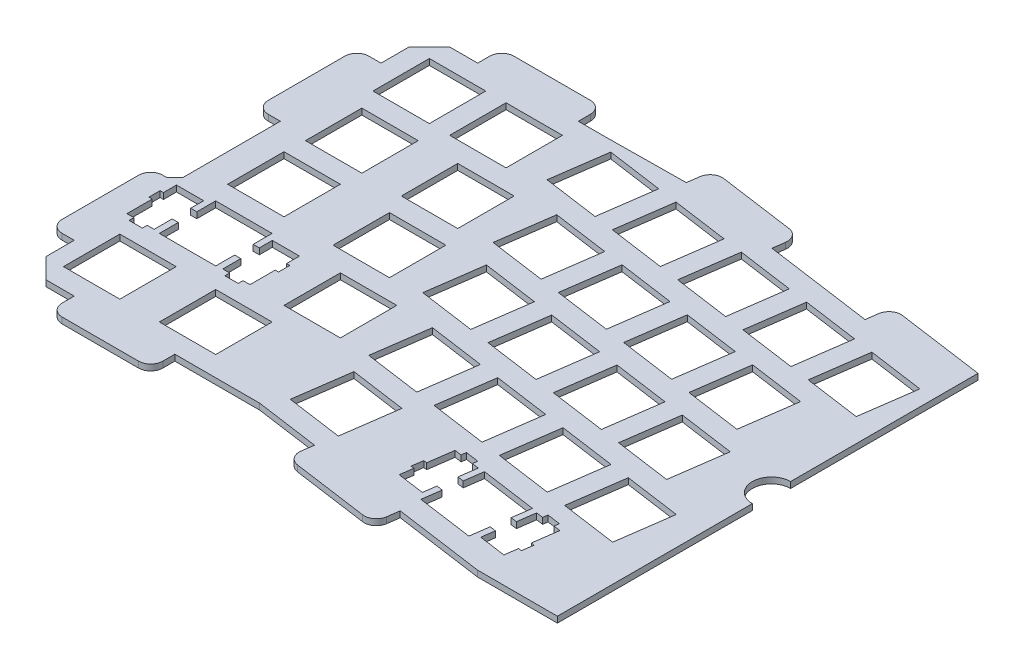
SolidWorks part; units mm, degrees
material "ABS PC"
ref_plane "Front Plane" through (0, 0, 0) normal (0, 0, 1) x (1, 0, 0)
ref_plane "Top Plane" through (0, 0, 0) normal (0, 1, 0) x (1, 0, 0)
ref_plane "Right Plane" through (0, 0, 0) normal (1, 0, 0) x (0, 0, -1)
sketch "Sketch1" plane through (0, 0, 0) normal (0, 1, 0) x (1, 0, 0)
  line L57 (39.046, 95.2051) -> (-4.333, 95.2051)
  line L58 (-4.333, 95.2051) -> (-4.333, -5)
  line L59 (-4.333, -5) -> (53.7464, -5)
  line L60 (53.7464, -5) -> (116.699, -13.8474)
  line L61 (116.699, -13.8474) -> (136.5182, -13.8474)
  line L62 (136.5182, -13.8474) -> (136.5182, 84.5577)
  line L63 (136.5182, 84.5577) -> (39.4665, 98.1974)
  line L64 (39.4665, 98.1974) -> (39.046, 95.2051)
  line L65 (39.046, 95.2051) -> (-4.333, 95.2051)
  line L66 (-4.333, 95.2051) -> (-4.333, -5)
  line L67 (-4.333, -5) -> (53.7464, -5)
  line L68 (53.7464, -5) -> (116.699, -13.8474)
  line L69 (116.699, -13.8474) -> (136.5182, -13.8474)
  line L70 (136.5182, -13.8474) -> (136.5182, 84.5577)
  line L71 (136.5182, 84.5577) -> (39.4665, 98.1974)
  line L72 (39.4665, 98.1974) -> (39.046, 95.2051)
  line L217 (136.5182, -26.9318) -> (136.5182, 108.4551) construction
  dimension "D1" = 0
extrude "Boss-Extrude1" add sketch "Sketch1" against normal blind 1.5
sketch "Sketch2" plane through (0, 0, 0) normal (0, -1, 0) x (-1, 0, 0)
  line L4 (-2.668, 52.1024) -> (-16.668, 52.1024)
  line L5 (-16.668, 52.1024) -> (-16.668, 38.1024)
  line L6 (-16.668, 38.1024) -> (-2.668, 38.1024)
  line L7 (-2.668, 38.1024) -> (-2.668, 52.1024)
  line L8 (-2.668, 52.1024) -> (-16.668, 52.1024)
  line L9 (-16.668, 52.1024) -> (-16.668, 38.1024)
  line L10 (-16.668, 38.1024) -> (-2.668, 38.1024)
  line L11 (-2.668, 38.1024) -> (-2.668, 52.1024)
  line L12 (-28.8632, 52.1024) -> (-42.8632, 52.1024)
  line L13 (-42.8632, 52.1024) -> (-42.8632, 38.1024)
  line L14 (-42.8632, 38.1024) -> (-28.8632, 38.1024)
  line L15 (-28.8632, 38.1024) -> (-28.8632, 52.1024)
  line L16 (-28.8632, 52.1024) -> (-42.8632, 52.1024)
  line L17 (-42.8632, 52.1024) -> (-42.8632, 38.1024)
  line L18 (-42.8632, 38.1024) -> (-28.8632, 38.1024)
  line L19 (-28.8632, 38.1024) -> (-28.8632, 52.1024)
  line L20 (-227.1855, 51.3524) -> (-241.1855, 51.3524)
  line L21 (-241.1855, 51.3524) -> (-241.1855, 37.3524)
  line L22 (-241.1855, 37.3524) -> (-227.1855, 37.3524)
  line L23 (-227.1855, 37.3524) -> (-227.1855, 51.3524)
  line L24 (-227.1855, 51.3524) -> (-241.1855, 51.3524)
  line L25 (-241.1855, 51.3524) -> (-241.1855, 37.3524)
  line L26 (-241.1855, 37.3524) -> (-227.1855, 37.3524)
  line L27 (-227.1855, 37.3524) -> (-227.1855, 51.3524)
  line L28 (-180.0695, 51.0381) -> (-178.1211, 64.9018)
  line L29 (-193.9333, 52.9865) -> (-180.0695, 51.0381)
  line L30 (-191.9848, 66.8503) -> (-193.9333, 52.9865)
  line L31 (-178.1211, 64.9018) -> (-191.9848, 66.8503)
  line L32 (-180.0695, 51.0381) -> (-178.1211, 64.9018)
  line L33 (-193.9333, 52.9865) -> (-180.0695, 51.0381)
  line L34 (-191.9848, 66.8503) -> (-193.9333, 52.9865)
  line L35 (-178.1211, 64.9018) -> (-191.9848, 66.8503)
  line L36 (-118.6152, 48.6476) -> (-104.7514, 50.596)
  line L37 (-120.5636, 62.5114) -> (-118.6152, 48.6476)
  line L38 (-106.6998, 64.4598) -> (-120.5636, 62.5114)
  line L39 (-104.7514, 50.596) -> (-106.6998, 64.4598)
  line L40 (-118.6152, 48.6476) -> (-104.7514, 50.596)
  line L41 (-120.5636, 62.5114) -> (-118.6152, 48.6476)
  line L42 (-106.6998, 64.4598) -> (-120.5636, 62.5114)
  line L43 (-104.7514, 50.596) -> (-106.6998, 64.4598)
  line L44 (-161.2042, 48.388) -> (-159.2557, 62.2517)
  line L45 (-175.0679, 50.3364) -> (-161.2042, 48.388)
  line L46 (-173.1195, 64.2001) -> (-175.0679, 50.3364)
  line L47 (-159.2557, 62.2517) -> (-173.1195, 64.2001)
  line L48 (-161.2042, 48.388) -> (-159.2557, 62.2517)
  line L49 (-175.0679, 50.3364) -> (-161.2042, 48.388)
  line L50 (-173.1195, 64.2001) -> (-175.0679, 50.3364)
  line L51 (-159.2557, 62.2517) -> (-173.1195, 64.2001)
  line L52 (-154.2536, 61.5467) -> (-156.2021, 47.683)
  line L53 (-140.3899, 59.5983) -> (-154.2536, 61.5467)
  line L54 (-142.3383, 45.7346) -> (-140.3899, 59.5983)
  line L55 (-156.2021, 47.683) -> (-142.3383, 45.7346)
  line L56 (-154.2536, 61.5467) -> (-156.2021, 47.683)
  line L57 (-140.3899, 59.5983) -> (-154.2536, 61.5467)
  line L58 (-142.3383, 45.7346) -> (-140.3899, 59.5983)
  line L59 (-156.2021, 47.683) -> (-142.3383, 45.7346)
  line L60 (-80.8836, 53.9505) -> (-67.0198, 55.899)
  line L61 (-82.832, 67.8143) -> (-80.8836, 53.9505)
  line L62 (-68.9683, 69.7627) -> (-82.832, 67.8143)
  line L63 (-67.0198, 55.899) -> (-68.9683, 69.7627)
  line L64 (-80.8836, 53.9505) -> (-67.0198, 55.899)
  line L65 (-82.832, 67.8143) -> (-80.8836, 53.9505)
  line L66 (-68.9683, 69.7627) -> (-82.832, 67.8143)
  line L67 (-67.0198, 55.899) -> (-68.9683, 69.7627)
  line L68 (-198.9348, 53.6888) -> (-196.9864, 67.5526)
  line L69 (-212.7985, 55.6372) -> (-198.9348, 53.6888)
  line L70 (-210.8501, 69.501) -> (-212.7985, 55.6372)
  line L71 (-196.9864, 67.5526) -> (-210.8501, 69.501)
  line L72 (-198.9348, 53.6888) -> (-196.9864, 67.5526)
  line L73 (-212.7985, 55.6372) -> (-198.9348, 53.6888)
  line L74 (-210.8501, 69.501) -> (-212.7985, 55.6372)
  line L75 (-196.9864, 67.5526) -> (-210.8501, 69.501)
  line L76 (-315.9639, 65.6408) -> (-329.9639, 65.6408)
  line L77 (-329.9639, 65.6408) -> (-329.9639, 51.6408)
  line L78 (-329.9639, 51.6408) -> (-315.9639, 51.6408)
  line L79 (-315.9639, 51.6408) -> (-315.9639, 65.6408)
  line L80 (-315.9639, 65.6408) -> (-329.9639, 65.6408)
  line L81 (-329.9639, 65.6408) -> (-329.9639, 51.6408)
  line L82 (-329.9639, 51.6408) -> (-315.9639, 51.6408)
  line L83 (-315.9639, 51.6408) -> (-315.9639, 65.6408)
  line L84 (-87.8343, 67.1107) -> (-101.698, 65.1623)
  line L85 (-85.8859, 53.247) -> (-87.8343, 67.1107)
  line L86 (-99.7496, 51.2985) -> (-85.8859, 53.247)
  line L87 (-101.698, 65.1623) -> (-99.7496, 51.2985)
  line L88 (-87.8343, 67.1107) -> (-101.698, 65.1623)
  line L89 (-85.8859, 53.247) -> (-87.8343, 67.1107)
  line L90 (-99.7496, 51.2985) -> (-85.8859, 53.247)
  line L91 (-101.698, 65.1623) -> (-99.7496, 51.2985)
  line L92 (-239.1873, 70.4036) -> (-253.1873, 70.4036)
  line L93 (-253.1873, 70.4036) -> (-253.1873, 56.4036)
  line L94 (-253.1873, 56.4036) -> (-239.1873, 56.4036)
  line L95 (-239.1873, 56.4036) -> (-239.1873, 70.4036)
  line L96 (-239.1873, 70.4036) -> (-253.1873, 70.4036)
  line L97 (-253.1873, 70.4036) -> (-253.1873, 56.4036)
  line L98 (-253.1873, 56.4036) -> (-239.1873, 56.4036)
  line L99 (-239.1873, 56.4036) -> (-239.1873, 70.4036)
  line L100 (-258.2384, 70.4036) -> (-272.2384, 70.4036)
  line L101 (-272.2384, 70.4036) -> (-272.2384, 56.4036)
  line L102 (-272.2384, 56.4036) -> (-258.2384, 56.4036)
  line L103 (-258.2384, 56.4036) -> (-258.2384, 70.4036)
  line L104 (-258.2384, 70.4036) -> (-272.2384, 70.4036)
  line L105 (-272.2384, 70.4036) -> (-272.2384, 56.4036)
  line L106 (-272.2384, 56.4036) -> (-258.2384, 56.4036)
  line L107 (-258.2384, 56.4036) -> (-258.2384, 70.4036)
  line L108 (-282.0529, 70.4036) -> (-296.0529, 70.4036)
  line L109 (-296.0529, 70.4036) -> (-296.0529, 56.4036)
  line L110 (-296.0529, 56.4036) -> (-282.0529, 56.4036)
  line L111 (-282.0529, 56.4036) -> (-282.0529, 70.4036)
  line L112 (-282.0529, 70.4036) -> (-296.0529, 70.4036)
  line L113 (-296.0529, 70.4036) -> (-296.0529, 56.4036)
  line L114 (-296.0529, 56.4036) -> (-282.0529, 56.4036)
  line L115 (-282.0529, 56.4036) -> (-282.0529, 70.4036)
  line L116 (-50.1, 72.4164) -> (-63.9638, 70.468)
  line L117 (-48.1516, 58.5526) -> (-50.1, 72.4164)
  line L118 (-62.0153, 56.6042) -> (-48.1516, 58.5526)
  line L119 (-63.9638, 70.468) -> (-62.0153, 56.6042)
  line L120 (-50.1, 72.4164) -> (-63.9638, 70.468)
  line L121 (-48.1516, 58.5526) -> (-50.1, 72.4164)
  line L122 (-62.0153, 56.6042) -> (-48.1516, 58.5526)
  line L123 (-63.9638, 70.468) -> (-62.0153, 56.6042)
  line L124 (-158.0197, -8.301) -> (-157.57, -5.1025)
  line L125 (-164.7049, -7.3597) -> (-158.0197, -8.301)
  line L126 (-164.2552, -4.1612) -> (-164.7049, -7.3597)
  line L127 (-165.7652, -3.9487) -> (-164.2552, -4.1612)
  line L128 (-166.4193, -8.6024) -> (-165.7652, -3.9487)
  line L129 (-180.283, -6.654) -> (-166.4193, -8.6024)
  line L130 (-179.6288, -1.9986) -> (-180.283, -6.654)
  line L131 (-181.1399, -1.7869) -> (-179.6288, -1.9986)
  line L132 (-181.5889, -4.9856) -> (-181.1399, -1.7869)
  line L133 (-188.2726, -4.0495) -> (-181.5889, -4.9856)
  line L134 (-187.8237, -0.8493) -> (-188.2726, -4.0495)
  line L135 (-188.6407, -0.7352) -> (-187.8237, -0.8493)
  line L136 (-188.2539, 2.0361) -> (-188.6407, -0.7352)
  line L137 (-187.4358, 1.922) -> (-188.2539, 2.0361)
  line L138 (-186.5659, 8.1321) -> (-187.4358, 1.922)
  line L139 (-184.8567, 7.8916) -> (-186.5659, 8.1321)
  line L140 (-184.6901, 9.0809) -> (-184.8567, 7.8916)
  line L141 (-181.4217, 8.6218) -> (-184.6901, 9.0809)
  line L142 (-181.5893, 7.4338) -> (-181.4217, 8.6218)
  line L143 (-179.8801, 7.1932) -> (-181.5893, 7.4338)
  line L144 (-180.5017, 2.7678) -> (-179.8801, 7.1932)
  line L145 (-178.9915, 2.5561) -> (-180.5017, 2.7678)
  line L146 (-178.338, 7.2102) -> (-178.9915, 2.5561)
  line L147 (-164.4743, 5.2618) -> (-178.338, 7.2102)
  line L148 (-165.1265, 0.6064) -> (-164.4743, 5.2618)
  line L149 (-163.6163, 0.3958) -> (-165.1265, 0.6064)
  line L150 (-162.9951, 4.8211) -> (-163.6163, 0.3958)
  line L151 (-161.287, 4.5816) -> (-162.9951, 4.8211)
  line L152 (-161.1202, 5.771) -> (-161.287, 4.5816)
  line L153 (-157.8529, 5.3113) -> (-161.1202, 5.771)
  line L154 (-158.0197, 4.1233) -> (-157.8529, 5.3113)
  line L155 (-156.3089, 3.8836) -> (-158.0197, 4.1233)
  line L156 (-157.1794, -2.3298) -> (-156.3089, 3.8836)
  line L157 (-156.3634, -2.4444) -> (-157.1794, -2.3298)
  line L158 (-156.754, -5.2171) -> (-156.3634, -2.4444)
  line L159 (-157.57, -5.1025) -> (-156.754, -5.2171)
  line L160 (-158.0197, -8.301) -> (-157.57, -5.1025)
  line L161 (-164.7049, -7.3597) -> (-158.0197, -8.301)
  line L162 (-164.2552, -4.1612) -> (-164.7049, -7.3597)
  line L163 (-165.7652, -3.9487) -> (-164.2552, -4.1612)
  line L164 (-166.4193, -8.6024) -> (-165.7652, -3.9487)
  line L165 (-180.283, -6.654) -> (-166.4193, -8.6024)
  line L166 (-179.6288, -1.9986) -> (-180.283, -6.654)
  line L167 (-181.1399, -1.7869) -> (-179.6288, -1.9986)
  line L168 (-181.5889, -4.9856) -> (-181.1399, -1.7869)
  line L169 (-188.2726, -4.0495) -> (-181.5889, -4.9856)
  line L170 (-187.8237, -0.8493) -> (-188.2726, -4.0495)
  line L171 (-188.6407, -0.7352) -> (-187.8237, -0.8493)
  line L172 (-188.2539, 2.0361) -> (-188.6407, -0.7352)
  line L173 (-187.4358, 1.922) -> (-188.2539, 2.0361)
  line L174 (-186.5659, 8.1321) -> (-187.4358, 1.922)
  line L175 (-184.8567, 7.8916) -> (-186.5659, 8.1321)
  line L176 (-184.6901, 9.0809) -> (-184.8567, 7.8916)
  line L177 (-181.4217, 8.6218) -> (-184.6901, 9.0809)
  line L178 (-181.5893, 7.4338) -> (-181.4217, 8.6218)
  line L179 (-179.8801, 7.1932) -> (-181.5893, 7.4338)
  line L180 (-180.5017, 2.7678) -> (-179.8801, 7.1932)
  line L181 (-178.9915, 2.5561) -> (-180.5017, 2.7678)
  line L182 (-178.338, 7.2102) -> (-178.9915, 2.5561)
  line L183 (-164.4743, 5.2618) -> (-178.338, 7.2102)
  line L184 (-165.1265, 0.6064) -> (-164.4743, 5.2618)
  line L185 (-163.6163, 0.3958) -> (-165.1265, 0.6064)
  line L186 (-162.9951, 4.8211) -> (-163.6163, 0.3958)
  line L187 (-161.287, 4.5816) -> (-162.9951, 4.8211)
  line L188 (-161.1202, 5.771) -> (-161.287, 4.5816)
  line L189 (-157.8529, 5.3113) -> (-161.1202, 5.771)
  line L190 (-158.0197, 4.1233) -> (-157.8529, 5.3113)
  line L191 (-156.3089, 3.8836) -> (-158.0197, 4.1233)
  line L192 (-157.1794, -2.3298) -> (-156.3089, 3.8836)
  line L193 (-156.3634, -2.4444) -> (-157.1794, -2.3298)
  line L194 (-156.754, -5.2171) -> (-156.3634, -2.4444)
  line L195 (-157.57, -5.1025) -> (-156.754, -5.2171)
  line L196 (-149.118, 65.9202) -> (-147.1695, 79.7839)
  line L197 (-162.9817, 67.8686) -> (-149.118, 65.9202)
  line L198 (-161.0333, 81.7324) -> (-162.9817, 67.8686)
  line L199 (-147.1695, 79.7839) -> (-161.0333, 81.7324)
  line L200 (-149.118, 65.9202) -> (-147.1695, 79.7839)
  line L201 (-162.9817, 67.8686) -> (-149.118, 65.9202)
  line L202 (-161.0333, 81.7324) -> (-162.9817, 67.8686)
  line L203 (-147.1695, 79.7839) -> (-161.0333, 81.7324)
  line L204 (-2.9533, 71.1536) -> (-16.9533, 71.1536)
  line L205 (-16.9533, 71.1536) -> (-16.9533, 57.1536)
  line L206 (-16.9533, 57.1536) -> (-2.9533, 57.1536)
  line L207 (-2.9533, 57.1536) -> (-2.9533, 71.1536)
  line L208 (-2.9533, 71.1536) -> (-16.9533, 71.1536)
  line L209 (-16.9533, 71.1536) -> (-16.9533, 57.1536)
  line L210 (-16.9533, 57.1536) -> (-2.9533, 57.1536)
  line L211 (-2.9533, 57.1536) -> (-2.9533, 71.1536)
  line L212 (-26.7687, 71.1536) -> (-40.7687, 71.1536)
  line L213 (-40.7687, 71.1536) -> (-40.7687, 57.1536)
  line L214 (-40.7687, 57.1536) -> (-26.7687, 57.1536)
  line L215 (-26.7687, 57.1536) -> (-26.7687, 71.1536)
  line L216 (-26.7687, 71.1536) -> (-40.7687, 71.1536)
  line L217 (-40.7687, 71.1536) -> (-40.7687, 57.1536)
  line L218 (-40.7687, 57.1536) -> (-26.7687, 57.1536)
  line L219 (-26.7687, 57.1536) -> (-26.7687, 71.1536)
  line L220 (-234.1361, 56.4036) -> (-220.1361, 56.4036)
  line L221 (-220.1361, 56.4036) -> (-220.1361, 70.4036)
  line L222 (-220.1361, 70.4036) -> (-234.1361, 70.4036)
  line L223 (-234.1361, 70.4036) -> (-234.1361, 56.4036)
  line L224 (-234.1361, 56.4036) -> (-220.1361, 56.4036)
  line L225 (-220.1361, 56.4036) -> (-220.1361, 70.4036)
  line L226 (-220.1361, 70.4036) -> (-234.1361, 70.4036)
  line L227 (-234.1361, 70.4036) -> (-234.1361, 56.4036)
  line L228 (-310.8196, 8.4872) -> (-324.8196, 8.4872)
  line L229 (-324.8196, 8.4872) -> (-324.8196, -5.5128)
  line L230 (-324.8196, -5.5128) -> (-310.8196, -5.5128)
  line L231 (-310.8196, -5.5128) -> (-310.8196, 8.4872)
  line L232 (-310.8196, 8.4872) -> (-324.8196, 8.4872)
  line L233 (-324.8196, 8.4872) -> (-324.8196, -5.5128)
  line L234 (-324.8196, -5.5128) -> (-310.8196, -5.5128)
  line L235 (-310.8196, -5.5128) -> (-310.8196, 8.4872)
  line L236 (-186.8504, 71.2271) -> (-184.9019, 85.0909)
  line L237 (-200.7141, 73.1755) -> (-186.8504, 71.2271)
  line L238 (-198.7657, 87.0393) -> (-200.7141, 73.1755)
  line L239 (-184.9019, 85.0909) -> (-198.7657, 87.0393)
  line L240 (-186.8504, 71.2271) -> (-184.9019, 85.0909)
  line L241 (-200.7141, 73.1755) -> (-186.8504, 71.2271)
  line L242 (-198.7657, 87.0393) -> (-200.7141, 73.1755)
  line L243 (-184.9019, 85.0909) -> (-198.7657, 87.0393)
  line L244 (-111.8336, 68.8397) -> (-97.9699, 70.7881)
  line L245 (-113.7821, 82.7035) -> (-111.8336, 68.8397)
  line L246 (-99.9183, 84.6519) -> (-113.7821, 82.7035)
  line L247 (-97.9699, 70.7881) -> (-99.9183, 84.6519)
  line L248 (-111.8336, 68.8397) -> (-97.9699, 70.7881)
  line L249 (-113.7821, 82.7035) -> (-111.8336, 68.8397)
  line L250 (-99.9183, 84.6519) -> (-113.7821, 82.7035)
  line L251 (-97.9699, 70.7881) -> (-99.9183, 84.6519)
  line L252 (-167.9848, 68.5776) -> (-166.0364, 82.4413)
  line L253 (-181.8485, 70.526) -> (-167.9848, 68.5776)
  line L254 (-179.9001, 84.3897) -> (-181.8485, 70.526)
  line L255 (-166.0364, 82.4413) -> (-179.9001, 84.3897)
  line L256 (-167.9848, 68.5776) -> (-166.0364, 82.4413)
  line L257 (-181.8485, 70.526) -> (-167.9848, 68.5776)
  line L258 (-179.9001, 84.3897) -> (-181.8485, 70.526)
  line L259 (-166.0364, 82.4413) -> (-179.9001, 84.3897)
  line L260 (-118.7828, 82.0008) -> (-132.6465, 80.0523)
  line L261 (-116.8343, 68.137) -> (-118.7828, 82.0008)
  line L262 (-130.6981, 66.1886) -> (-116.8343, 68.137)
  line L263 (-132.6465, 80.0523) -> (-130.6981, 66.1886)
  line L264 (-118.7828, 82.0008) -> (-132.6465, 80.0523)
  line L265 (-116.8343, 68.137) -> (-118.7828, 82.0008)
  line L266 (-130.6981, 66.1886) -> (-116.8343, 68.137)
  line L267 (-132.6465, 80.0523) -> (-130.6981, 66.1886)
  line L268 (-109.5931, 1.5905) -> (-111.1042, 1.3782)
  line L269 (-110.2481, 6.2457) -> (-109.5931, 1.5905)
  line L270 (-96.3844, 8.1942) -> (-110.2481, 6.2457)
  line L271 (-95.7296, 3.5418) -> (-96.3844, 8.1942)
  line L272 (-94.2205, 3.7527) -> (-95.7296, 3.5418)
  line L273 (-94.8425, 8.1806) -> (-94.2205, 3.7527)
  line L274 (-93.1334, 8.4204) -> (-94.8425, 8.1806)
  line L275 (-93.3014, 9.6083) -> (-93.1334, 8.4204)
  line L276 (-90.0324, 10.0671) -> (-93.3014, 9.6083)
  line L277 (-89.8659, 8.8792) -> (-90.0324, 10.0671)
  line L278 (-88.1583, 9.1189) -> (-89.8659, 8.8792)
  line L279 (-87.2845, 2.9106) -> (-88.1583, 9.1189)
  line L280 (-86.4675, 3.0249) -> (-87.2845, 2.9106)
  line L281 (-86.0773, 0.2521) -> (-86.4675, 3.0249)
  line L282 (-86.8948, 0.1364) -> (-86.0773, 0.2521)
  line L283 (-86.4453, -3.0609) -> (-86.8948, 0.1364)
  line L284 (-93.1306, -4.0007) -> (-86.4453, -3.0609)
  line L285 (-93.5796, -0.8021) -> (-93.1306, -4.0007)
  line L286 (-95.0907, -1.0143) -> (-93.5796, -0.8021)
  line L287 (-94.4357, -5.6696) -> (-95.0907, -1.0143)
  line L288 (-108.2995, -7.618) -> (-94.4357, -5.6696)
  line L289 (-108.9549, -2.9641) -> (-108.2995, -7.618)
  line L290 (-110.465, -3.1765) -> (-108.9549, -2.9641)
  line L291 (-110.0157, -6.3751) -> (-110.465, -3.1765)
  line L292 (-116.699, -7.3155) -> (-110.0157, -6.3751)
  line L293 (-117.1503, -4.1155) -> (-116.699, -7.3155)
  line L294 (-117.9673, -4.2313) -> (-117.1503, -4.1155)
  line L295 (-118.3576, -1.4586) -> (-117.9673, -4.2313)
  line L296 (-117.5405, -1.3441) -> (-118.3576, -1.4586)
  line L297 (-118.4121, 4.8656) -> (-117.5405, -1.3441)
  line L298 (-116.7015, 5.1061) -> (-118.4121, 4.8656)
  line L299 (-116.8685, 6.2954) -> (-116.7015, 5.1061)
  line L300 (-113.6013, 6.7543) -> (-116.8685, 6.2954)
  line L301 (-113.4343, 5.5663) -> (-113.6013, 6.7543)
  line L302 (-111.7252, 5.8061) -> (-113.4343, 5.5663)
  line L303 (-111.1042, 1.3782) -> (-111.7252, 5.8061)
  line L304 (-109.5931, 1.5905) -> (-111.1042, 1.3782)
  line L305 (-110.2481, 6.2457) -> (-109.5931, 1.5905)
  line L306 (-96.3844, 8.1942) -> (-110.2481, 6.2457)
  line L307 (-95.7296, 3.5418) -> (-96.3844, 8.1942)
  line L308 (-94.2205, 3.7527) -> (-95.7296, 3.5418)
  line L309 (-94.8425, 8.1806) -> (-94.2205, 3.7527)
  line L310 (-93.1334, 8.4204) -> (-94.8425, 8.1806)
  line L311 (-93.3014, 9.6083) -> (-93.1334, 8.4204)
  line L312 (-90.0324, 10.0671) -> (-93.3014, 9.6083)
  line L313 (-89.8659, 8.8792) -> (-90.0324, 10.0671)
  line L314 (-88.1583, 9.1189) -> (-89.8659, 8.8792)
  line L315 (-87.2845, 2.9106) -> (-88.1583, 9.1189)
  line L316 (-86.4675, 3.0249) -> (-87.2845, 2.9106)
  line L317 (-86.0773, 0.2521) -> (-86.4675, 3.0249)
  line L318 (-86.8948, 0.1364) -> (-86.0773, 0.2521)
  line L319 (-86.4453, -3.0609) -> (-86.8948, 0.1364)
  line L320 (-93.1306, -4.0007) -> (-86.4453, -3.0609)
  line L321 (-93.5796, -0.8021) -> (-93.1306, -4.0007)
  line L322 (-95.0907, -1.0143) -> (-93.5796, -0.8021)
  line L323 (-94.4357, -5.6696) -> (-95.0907, -1.0143)
  line L324 (-108.2995, -7.618) -> (-94.4357, -5.6696)
  line L325 (-108.9549, -2.9641) -> (-108.2995, -7.618)
  line L326 (-110.465, -3.1765) -> (-108.9549, -2.9641)
  line L327 (-110.0157, -6.3751) -> (-110.465, -3.1765)
  line L328 (-116.699, -7.3155) -> (-110.0157, -6.3751)
  line L329 (-117.1503, -4.1155) -> (-116.699, -7.3155)
  line L330 (-117.9673, -4.2313) -> (-117.1503, -4.1155)
  line L331 (-118.3576, -1.4586) -> (-117.9673, -4.2313)
  line L332 (-117.5405, -1.3441) -> (-118.3576, -1.4586)
  line L333 (-118.4121, 4.8656) -> (-117.5405, -1.3441)
  line L334 (-116.7015, 5.1061) -> (-118.4121, 4.8656)
  line L335 (-116.8685, 6.2954) -> (-116.7015, 5.1061)
  line L336 (-113.6013, 6.7543) -> (-116.8685, 6.2954)
  line L337 (-113.4343, 5.5663) -> (-113.6013, 6.7543)
  line L338 (-111.7252, 5.8061) -> (-113.4343, 5.5663)
  line L339 (-111.1042, 1.3782) -> (-111.7252, 5.8061)
  line L340 (-70.5695, -2.3152) -> (-56.7058, -0.3668)
  line L341 (-72.518, 11.5486) -> (-70.5695, -2.3152)
  line L342 (-58.6542, 13.497) -> (-72.518, 11.5486)
  line L343 (-56.7058, -0.3668) -> (-58.6542, 13.497)
  line L344 (-70.5695, -2.3152) -> (-56.7058, -0.3668)
  line L345 (-72.518, 11.5486) -> (-70.5695, -2.3152)
  line L346 (-58.6542, 13.497) -> (-72.518, 11.5486)
  line L347 (-56.7058, -0.3668) -> (-58.6542, 13.497)
  line L348 (-197.0785, -4.2966) -> (-195.1301, 9.5671)
  line L349 (-210.9422, -2.3482) -> (-197.0785, -4.2966)
  line L350 (-208.9938, 11.5155) -> (-210.9422, -2.3482)
  line L351 (-195.1301, 9.5671) -> (-208.9938, 11.5155)
  line L352 (-197.0785, -4.2966) -> (-195.1301, 9.5671)
  line L353 (-210.9422, -2.3482) -> (-197.0785, -4.2966)
  line L354 (-208.9938, 11.5155) -> (-210.9422, -2.3482)
  line L355 (-195.1301, 9.5671) -> (-208.9938, 11.5155)
  line L356 (-272.7173, 8.4872) -> (-286.7173, 8.4872)
  line L357 (-286.7173, 8.4872) -> (-286.7173, -5.5128)
  line L358 (-286.7173, -5.5128) -> (-272.7173, -5.5128)
  line L359 (-272.7173, -5.5128) -> (-272.7173, 8.4872)
  line L360 (-272.7173, 8.4872) -> (-286.7173, 8.4872)
  line L361 (-286.7173, 8.4872) -> (-286.7173, -5.5128)
  line L362 (-286.7173, -5.5128) -> (-272.7173, -5.5128)
  line L363 (-272.7173, -5.5128) -> (-272.7173, 8.4872)
  line L364 (-305.7685, -5.5128) -> (-291.7685, -5.5128)
  line L365 (-291.7685, -5.5128) -> (-291.7685, 8.4872)
  line L366 (-291.7685, 8.4872) -> (-305.7685, 8.4872)
  line L367 (-305.7685, 8.4872) -> (-305.7685, -5.5128)
  line L368 (-305.7685, -5.5128) -> (-291.7685, -5.5128)
  line L369 (-291.7685, -5.5128) -> (-291.7685, 8.4872)
  line L370 (-291.7685, 8.4872) -> (-305.7685, 8.4872)
  line L371 (-305.7685, 8.4872) -> (-305.7685, -5.5128)
  line L372 (-315.9639, 89.4547) -> (-329.9639, 89.4547)
  line L373 (-329.9639, 89.4547) -> (-329.9639, 75.4547)
  line L374 (-329.9639, 75.4547) -> (-315.9639, 75.4547)
  line L375 (-315.9639, 75.4547) -> (-315.9639, 89.4547)
  line L376 (-315.9639, 89.4547) -> (-329.9639, 89.4547)
  line L377 (-329.9639, 89.4547) -> (-329.9639, 75.4547)
  line L378 (-329.9639, 75.4547) -> (-315.9639, 75.4547)
  line L379 (-315.9639, 75.4547) -> (-315.9639, 89.4547)
  line L380 (-74.102, 74.143) -> (-60.2383, 76.0914)
  line L381 (-76.0505, 88.0067) -> (-74.102, 74.143)
  line L382 (-62.1867, 89.9552) -> (-76.0505, 88.0067)
  line L383 (-60.2383, 76.0914) -> (-62.1867, 89.9552)
  line L384 (-74.102, 74.143) -> (-60.2383, 76.0914)
  line L385 (-76.0505, 88.0067) -> (-74.102, 74.143)
  line L386 (-62.1867, 89.9552) -> (-76.0505, 88.0067)
  line L387 (-60.2383, 76.0914) -> (-62.1867, 89.9552)
  line L388 (-205.7162, 73.88) -> (-203.7677, 87.7438)
  line L389 (-219.5799, 75.8285) -> (-205.7162, 73.88)
  line L390 (-217.6315, 89.6922) -> (-219.5799, 75.8285)
  line L391 (-203.7677, 87.7438) -> (-217.6315, 89.6922)
  line L392 (-205.7162, 73.88) -> (-203.7677, 87.7438)
  line L393 (-219.5799, 75.8285) -> (-205.7162, 73.88)
  line L394 (-217.6315, 89.6922) -> (-219.5799, 75.8285)
  line L395 (-203.7677, 87.7438) -> (-217.6315, 89.6922)
  line L396 (-81.0528, 87.3033) -> (-94.9166, 85.3549)
  line L397 (-79.1044, 73.4396) -> (-81.0528, 87.3033)
  line L398 (-92.9682, 71.4911) -> (-79.1044, 73.4396)
  line L399 (-94.9166, 85.3549) -> (-92.9682, 71.4911)
  line L400 (-81.0528, 87.3033) -> (-94.9166, 85.3549)
  line L401 (-79.1044, 73.4396) -> (-81.0528, 87.3033)
  line L402 (-92.9682, 71.4911) -> (-79.1044, 73.4396)
  line L403 (-94.9166, 85.3549) -> (-92.9682, 71.4911)
  line L404 (0.0015, 14.0032) -> (-13.9985, 14.0032)
  line L405 (-13.9985, 14.0032) -> (-13.9985, 0.0032)
  line L406 (-13.9985, 0.0032) -> (0.0015, 0.0032)
  line L407 (0.0015, 0.0032) -> (0.0015, 14.0032)
  line L408 (0.0015, 14.0032) -> (-13.9985, 14.0032)
  line L409 (-13.9985, 14.0032) -> (-13.9985, 0.0032)
  line L410 (-13.9985, 0.0032) -> (0.0015, 0.0032)
  line L411 (0.0015, 0.0032) -> (0.0015, 14.0032)
  line L412 (-23.8153, 14) -> (-37.8153, 14)
  line L413 (-37.8153, 14) -> (-37.8153, 0)
  line L414 (-37.8153, 0) -> (-23.8153, 0)
  line L415 (-23.8153, 0) -> (-23.8153, 14)
  line L416 (-23.8153, 14) -> (-37.8153, 14)
  line L417 (-37.8153, 14) -> (-37.8153, 0)
  line L418 (-37.8153, 0) -> (-23.8153, 0)
  line L419 (-23.8153, 0) -> (-23.8153, 14)
  line L420 (-229.8527, 13.25) -> (-243.8527, 13.25)
  line L421 (-243.8527, 13.25) -> (-243.8527, -0.75)
  line L422 (-243.8527, -0.75) -> (-229.8527, -0.75)
  line L423 (-229.8527, -0.75) -> (-229.8527, 13.25)
  line L424 (-229.8527, 13.25) -> (-243.8527, 13.25)
  line L425 (-243.8527, 13.25) -> (-243.8527, -0.75)
  line L426 (-243.8527, -0.75) -> (-229.8527, -0.75)
  line L427 (-229.8527, -0.75) -> (-229.8527, 13.25)
  line L428 (-262.9019, -0.75) -> (-248.9019, -0.75)
  line L429 (-248.9019, -0.75) -> (-248.9019, 13.25)
  line L430 (-248.9019, 13.25) -> (-262.9019, 13.25)
  line L431 (-262.9019, 13.25) -> (-262.9019, -0.75)
  line L432 (-262.9019, -0.75) -> (-248.9019, -0.75)
  line L433 (-248.9019, -0.75) -> (-248.9019, 13.25)
  line L434 (-248.9019, 13.25) -> (-262.9019, 13.25)
  line L435 (-262.9019, 13.25) -> (-262.9019, -0.75)
  line L436 (-226.8054, 89.4547) -> (-240.8054, 89.4547)
  line L437 (-240.8054, 89.4547) -> (-240.8054, 75.4547)
  line L438 (-240.8054, 75.4547) -> (-226.8054, 75.4547)
  line L439 (-226.8054, 75.4547) -> (-226.8054, 89.4547)
  line L440 (-226.8054, 89.4547) -> (-240.8054, 89.4547)
  line L441 (-240.8054, 89.4547) -> (-240.8054, 75.4547)
  line L442 (-240.8054, 75.4547) -> (-226.8054, 75.4547)
  line L443 (-226.8054, 75.4547) -> (-226.8054, 89.4547)
  line L444 (-245.8537, 89.4547) -> (-259.8537, 89.4547)
  line L445 (-259.8537, 89.4547) -> (-259.8537, 75.4547)
  line L446 (-259.8537, 75.4547) -> (-245.8537, 75.4547)
  line L447 (-245.8537, 75.4547) -> (-245.8537, 89.4547)
  line L448 (-245.8537, 89.4547) -> (-259.8537, 89.4547)
  line L449 (-259.8537, 89.4547) -> (-259.8537, 75.4547)
  line L450 (-259.8537, 75.4547) -> (-245.8537, 75.4547)
  line L451 (-245.8537, 75.4547) -> (-245.8537, 89.4547)
  line L452 (-264.9058, 89.4547) -> (-278.9058, 89.4547)
  line L453 (-278.9058, 89.4547) -> (-278.9058, 75.4547)
  line L454 (-278.9058, 75.4547) -> (-264.9058, 75.4547)
  line L455 (-264.9058, 75.4547) -> (-264.9058, 89.4547)
  line L456 (-264.9058, 89.4547) -> (-278.9058, 89.4547)
  line L457 (-278.9058, 89.4547) -> (-278.9058, 75.4547)
  line L458 (-278.9058, 75.4547) -> (-264.9058, 75.4547)
  line L459 (-264.9058, 75.4547) -> (-264.9058, 89.4547)
  line L460 (-297.957, 75.4547) -> (-283.957, 75.4547)
  line L461 (-283.957, 75.4547) -> (-283.957, 89.4547)
  line L462 (-283.957, 89.4547) -> (-297.957, 89.4547)
  line L463 (-297.957, 89.4547) -> (-297.957, 75.4547)
  line L464 (-297.957, 75.4547) -> (-283.957, 75.4547)
  line L465 (-283.957, 75.4547) -> (-283.957, 89.4547)
  line L466 (-283.957, 89.4547) -> (-297.957, 89.4547)
  line L467 (-297.957, 89.4547) -> (-297.957, 75.4547)
  line L468 (-108.5923, 11.5823) -> (-94.7285, 13.5308)
  line L469 (-110.5407, 25.4461) -> (-108.5923, 11.5823)
  line L470 (-96.6769, 27.3945) -> (-110.5407, 25.4461)
  line L471 (-94.7285, 13.5308) -> (-96.6769, 27.3945)
  line L472 (-108.5923, 11.5823) -> (-94.7285, 13.5308)
  line L473 (-110.5407, 25.4461) -> (-108.5923, 11.5823)
  line L474 (-96.6769, 27.3945) -> (-110.5407, 25.4461)
  line L475 (-94.7285, 13.5308) -> (-96.6769, 27.3945)
  line L476 (-161.7885, 9.9912) -> (-159.8401, 23.8549)
  line L477 (-175.6523, 11.9396) -> (-161.7885, 9.9912)
  line L478 (-173.7039, 25.8034) -> (-175.6523, 11.9396)
  line L479 (-159.8401, 23.8549) -> (-173.7039, 25.8034)
  line L480 (-161.7885, 9.9912) -> (-159.8401, 23.8549)
  line L481 (-175.6523, 11.9396) -> (-161.7885, 9.9912)
  line L482 (-173.7039, 25.8034) -> (-175.6523, 11.9396)
  line L483 (-159.8401, 23.8549) -> (-173.7039, 25.8034)
  line L484 (-127.4602, 8.9301) -> (-113.5965, 10.8786)
  line L485 (-129.4086, 22.7939) -> (-127.4602, 8.9301)
  line L486 (-115.5449, 24.7423) -> (-129.4086, 22.7939)
  line L487 (-113.5965, 10.8786) -> (-115.5449, 24.7423)
  line L488 (-127.4602, 8.9301) -> (-113.5965, 10.8786)
  line L489 (-129.4086, 22.7939) -> (-127.4602, 8.9301)
  line L490 (-115.5449, 24.7423) -> (-129.4086, 22.7939)
  line L491 (-113.5965, 10.8786) -> (-115.5449, 24.7423)
  line L492 (-154.8387, 23.1518) -> (-156.7871, 9.2881)
  line L493 (-140.975, 21.2034) -> (-154.8387, 23.1518)
  line L494 (-142.9234, 7.3397) -> (-140.975, 21.2034)
  line L495 (-156.7871, 9.2881) -> (-142.9234, 7.3397)
  line L496 (-154.8387, 23.1518) -> (-156.7871, 9.2881)
  line L497 (-140.975, 21.2034) -> (-154.8387, 23.1518)
  line L498 (-142.9234, 7.3397) -> (-140.975, 21.2034)
  line L499 (-156.7871, 9.2881) -> (-142.9234, 7.3397)
  line L500 (-55.2337, 76.7955) -> (-41.37, 78.7439)
  line L501 (-57.1821, 90.6593) -> (-55.2337, 76.7955)
  line L502 (-43.3184, 92.6077) -> (-57.1821, 90.6593)
  line L503 (-41.37, 78.7439) -> (-43.3184, 92.6077)
  line L504 (-55.2337, 76.7955) -> (-41.37, 78.7439)
  line L505 (-57.1821, 90.6593) -> (-55.2337, 76.7955)
  line L506 (-43.3184, 92.6077) -> (-57.1821, 90.6593)
  line L507 (-41.37, 78.7439) -> (-43.3184, 92.6077)
  line L508 (-0.667, 90.2051) -> (-14.667, 90.2051)
  line L509 (-14.667, 90.2051) -> (-14.667, 76.2051)
  line L510 (-14.667, 76.2051) -> (-0.667, 76.2051)
  line L511 (-0.667, 76.2051) -> (-0.667, 90.2051)
  line L512 (-0.667, 90.2051) -> (-14.667, 90.2051)
  line L513 (-14.667, 90.2051) -> (-14.667, 76.2051)
  line L514 (-14.667, 76.2051) -> (-0.667, 76.2051)
  line L515 (-0.667, 76.2051) -> (-0.667, 90.2051)
  line L516 (-33.7182, 76.2047) -> (-19.7182, 76.2047)
  line L517 (-19.7182, 76.2047) -> (-19.7182, 90.2047)
  line L518 (-19.7182, 90.2047) -> (-33.7182, 90.2047)
  line L519 (-33.7182, 90.2047) -> (-33.7182, 76.2047)
  line L520 (-33.7182, 76.2047) -> (-19.7182, 76.2047)
  line L521 (-19.7182, 76.2047) -> (-19.7182, 90.2047)
  line L522 (-19.7182, 90.2047) -> (-33.7182, 90.2047)
  line L523 (-33.7182, 90.2047) -> (-33.7182, 76.2047)
  line L524 (-199.5201, 15.2924) -> (-197.5716, 29.1561)
  line L525 (-213.3838, 17.2408) -> (-199.5201, 15.2924)
  line L526 (-211.4354, 31.1046) -> (-213.3838, 17.2408)
  line L527 (-197.5716, 29.1561) -> (-211.4354, 31.1046)
  line L528 (-199.5201, 15.2924) -> (-197.5716, 29.1561)
  line L529 (-213.3838, 17.2408) -> (-199.5201, 15.2924)
  line L530 (-211.4354, 31.1046) -> (-213.3838, 17.2408)
  line L531 (-197.5716, 29.1561) -> (-211.4354, 31.1046)
  line L532 (-291.5785, 27.5384) -> (-305.5785, 27.5384)
  line L533 (-305.5785, 27.5384) -> (-305.5785, 13.5384)
  line L534 (-305.5785, 13.5384) -> (-291.5785, 13.5384)
  line L535 (-291.5785, 13.5384) -> (-291.5785, 27.5384)
  line L536 (-291.5785, 27.5384) -> (-305.5785, 27.5384)
  line L537 (-305.5785, 27.5384) -> (-305.5785, 13.5384)
  line L538 (-305.5785, 13.5384) -> (-291.5785, 13.5384)
  line L539 (-291.5785, 13.5384) -> (-291.5785, 27.5384)
  line L540 (-89.7287, 14.2318) -> (-75.865, 16.1803)
  line L541 (-91.6772, 28.0956) -> (-89.7287, 14.2318)
  line L542 (-77.8134, 30.044) -> (-91.6772, 28.0956)
  line L543 (-75.865, 16.1803) -> (-77.8134, 30.044)
  line L544 (-89.7287, 14.2318) -> (-75.865, 16.1803)
  line L545 (-91.6772, 28.0956) -> (-89.7287, 14.2318)
  line L546 (-77.8134, 30.044) -> (-91.6772, 28.0956)
  line L547 (-75.865, 16.1803) -> (-77.8134, 30.044)
  line L548 (-192.5702, 28.4546) -> (-194.5187, 14.5909)
  line L549 (-178.7065, 26.5062) -> (-192.5702, 28.4546)
  line L550 (-180.6549, 12.6425) -> (-178.7065, 26.5062)
  line L551 (-194.5187, 14.5909) -> (-180.6549, 12.6425)
  line L552 (-192.5702, 28.4546) -> (-194.5187, 14.5909)
  line L553 (-178.7065, 26.5062) -> (-192.5702, 28.4546)
  line L554 (-180.6549, 12.6425) -> (-178.7065, 26.5062)
  line L555 (-194.5187, 14.5909) -> (-180.6549, 12.6425)
  line L556 (-58.9503, 32.6922) -> (-72.814, 30.7438)
  line L557 (-57.0019, 18.8284) -> (-58.9503, 32.6922)
  line L558 (-70.8656, 16.88) -> (-57.0019, 18.8284)
  line L559 (-72.814, 30.7438) -> (-70.8656, 16.88)
  line L560 (-58.9503, 32.6922) -> (-72.814, 30.7438)
  line L561 (-57.0019, 18.8284) -> (-58.9503, 32.6922)
  line L562 (-70.8656, 16.88) -> (-57.0019, 18.8284)
  line L563 (-72.814, 30.7438) -> (-70.8656, 16.88)
  line L564 (-239.1873, 32.3012) -> (-253.1873, 32.3012)
  line L565 (-253.1873, 32.3012) -> (-253.1873, 18.3012)
  line L566 (-253.1873, 18.3012) -> (-239.1873, 18.3012)
  line L567 (-239.1873, 18.3012) -> (-239.1873, 32.3012)
  line L568 (-239.1873, 32.3012) -> (-253.1873, 32.3012)
  line L569 (-253.1873, 32.3012) -> (-253.1873, 18.3012)
  line L570 (-253.1873, 18.3012) -> (-239.1873, 18.3012)
  line L571 (-239.1873, 18.3012) -> (-239.1873, 32.3012)
  line L572 (-263.0017, 32.3012) -> (-277.0017, 32.3012)
  line L573 (-277.0017, 32.3012) -> (-277.0017, 18.3012)
  line L574 (-277.0017, 18.3012) -> (-263.0017, 18.3012)
  line L575 (-263.0017, 18.3012) -> (-263.0017, 32.3012)
  line L576 (-263.0017, 32.3012) -> (-277.0017, 32.3012)
  line L577 (-277.0017, 32.3012) -> (-277.0017, 18.3012)
  line L578 (-277.0017, 18.3012) -> (-263.0017, 18.3012)
  line L579 (-263.0017, 18.3012) -> (-263.0017, 32.3012)
  line L580 (-120.6811, 29.1192) -> (-106.8174, 31.0676)
  line L581 (-122.6296, 42.9829) -> (-120.6811, 29.1192)
  line L582 (-108.7658, 44.9313) -> (-122.6296, 42.9829)
  line L583 (-106.8174, 31.0676) -> (-108.7658, 44.9313)
  line L584 (-120.6811, 29.1192) -> (-106.8174, 31.0676)
  line L585 (-122.6296, 42.9829) -> (-120.6811, 29.1192)
  line L586 (-108.7658, 44.9313) -> (-122.6296, 42.9829)
  line L587 (-106.8174, 31.0676) -> (-108.7658, 44.9313)
  line L588 (-149.7055, 27.5327) -> (-147.7571, 41.3964)
  line L589 (-163.5692, 29.4811) -> (-149.7055, 27.5327)
  line L590 (-161.6208, 43.3449) -> (-163.5692, 29.4811)
  line L591 (-147.7571, 41.3964) -> (-161.6208, 43.3449)
  line L592 (-149.7055, 27.5327) -> (-147.7571, 41.3964)
  line L593 (-163.5692, 29.4811) -> (-149.7055, 27.5327)
  line L594 (-161.6208, 43.3449) -> (-163.5692, 29.4811)
  line L595 (-147.7571, 41.3964) -> (-161.6208, 43.3449)
  line L596 (-35.7223, 33.0512) -> (-49.7223, 33.0512)
  line L597 (-49.7223, 33.0512) -> (-49.7223, 19.0512)
  line L598 (-49.7223, 19.0512) -> (-35.7223, 19.0512)
  line L599 (-35.7223, 19.0512) -> (-35.7223, 33.0512)
  line L600 (-35.7223, 33.0512) -> (-49.7223, 33.0512)
  line L601 (-49.7223, 33.0512) -> (-49.7223, 19.0512)
  line L602 (-49.7223, 19.0512) -> (-35.7223, 19.0512)
  line L603 (-35.7223, 19.0512) -> (-35.7223, 33.0512)
  line L604 (-234.2319, 18.3012) -> (-220.2319, 18.3012)
  line L605 (-220.2319, 18.3012) -> (-220.2319, 32.3012)
  line L606 (-220.2319, 32.3012) -> (-234.2319, 32.3012)
  line L607 (-234.2319, 32.3012) -> (-234.2319, 18.3012)
  line L608 (-234.2319, 18.3012) -> (-220.2319, 18.3012)
  line L609 (-220.2319, 18.3012) -> (-220.2319, 32.3012)
  line L610 (-220.2319, 32.3012) -> (-234.2319, 32.3012)
  line L611 (-234.2319, 32.3012) -> (-234.2319, 18.3012)
  line L612 (-29.4211, 31.5821) -> (-29.4211, 28.3519)
  line L613 (-22.6712, 31.5821) -> (-29.4211, 31.5821)
  line L614 (-22.6712, 28.3519) -> (-22.6712, 31.5821)
  line L615 (-21.1456, 28.3519) -> (-22.6712, 28.3519)
  line L616 (-21.1456, 33.0512) -> (-21.1456, 28.3519)
  line L617 (-7.1456, 33.0512) -> (-21.1456, 33.0512)
  line L618 (-7.1456, 28.3521) -> (-7.1456, 33.0512)
  line L619 (-5.62, 28.3521) -> (-7.1456, 28.3521)
  line L620 (-5.62, 31.5823) -> (-5.62, 28.3521)
  line L621 (1.13, 31.5823) -> (-5.62, 31.5823)
  line L622 (1.13, 28.3521) -> (1.13, 31.5823)
  line L623 (1.9556, 28.3521) -> (1.13, 28.3521)
  line L624 (1.9556, 25.552) -> (1.9556, 28.3521)
  line L625 (1.13, 25.552) -> (1.9556, 25.552)
  line L626 (1.13, 19.2814) -> (1.13, 25.552)
  line L627 (-0.594, 19.2814) -> (1.13, 19.2814)
  line L628 (-0.594, 18.081) -> (-0.594, 19.2814)
  line L629 (-3.8945, 18.081) -> (-0.594, 18.081)
  line L630 (-3.8945, 19.2814) -> (-3.8945, 18.081)
  line L631 (-5.62, 19.2814) -> (-3.8945, 19.2814)
  line L632 (-5.62, 23.7519) -> (-5.62, 19.2814)
  line L633 (-7.1456, 23.7519) -> (-5.62, 23.7519)
  line L634 (-7.1456, 19.0512) -> (-7.1456, 23.7519)
  line L635 (-21.1456, 19.0512) -> (-7.1456, 19.0512)
  line L636 (-21.1456, 23.7519) -> (-21.1456, 19.0512)
  line L637 (-22.6712, 23.7519) -> (-21.1456, 23.7519)
  line L638 (-22.6712, 19.2814) -> (-22.6712, 23.7519)
  line L639 (-24.3952, 19.2814) -> (-22.6712, 19.2814)
  line L640 (-24.3952, 18.081) -> (-24.3952, 19.2814)
  line L641 (-27.6959, 18.081) -> (-24.3952, 18.081)
  line L642 (-27.6959, 19.2814) -> (-27.6959, 18.081)
  line L643 (-29.4211, 19.2814) -> (-27.6959, 19.2814)
  line L644 (-29.4211, 25.552) -> (-29.4211, 19.2814)
  line L645 (-30.2453, 25.552) -> (-29.4211, 25.552)
  line L646 (-30.2453, 28.3519) -> (-30.2453, 25.552)
  line L647 (-29.4211, 28.3519) -> (-30.2453, 28.3519)
  line L648 (-29.4211, 31.5821) -> (-29.4211, 28.3519)
  line L649 (-22.6712, 31.5821) -> (-29.4211, 31.5821)
  line L650 (-22.6712, 28.3519) -> (-22.6712, 31.5821)
  line L651 (-21.1456, 28.3519) -> (-22.6712, 28.3519)
  line L652 (-21.1456, 33.0512) -> (-21.1456, 28.3519)
  line L653 (-7.1456, 33.0512) -> (-21.1456, 33.0512)
  line L654 (-7.1456, 28.3521) -> (-7.1456, 33.0512)
  line L655 (-5.62, 28.3521) -> (-7.1456, 28.3521)
  line L656 (-5.62, 31.5823) -> (-5.62, 28.3521)
  line L657 (1.13, 31.5823) -> (-5.62, 31.5823)
  line L658 (1.13, 28.3521) -> (1.13, 31.5823)
  line L659 (1.9556, 28.3521) -> (1.13, 28.3521)
  line L660 (1.9556, 25.552) -> (1.9556, 28.3521)
  line L661 (1.13, 25.552) -> (1.9556, 25.552)
  line L662 (1.13, 19.2814) -> (1.13, 25.552)
  line L663 (-0.594, 19.2814) -> (1.13, 19.2814)
  line L664 (-0.594, 18.081) -> (-0.594, 19.2814)
  line L665 (-3.8945, 18.081) -> (-0.594, 18.081)
  line L666 (-3.8945, 19.2814) -> (-3.8945, 18.081)
  line L667 (-5.62, 19.2814) -> (-3.8945, 19.2814)
  line L668 (-5.62, 23.7519) -> (-5.62, 19.2814)
  line L669 (-7.1456, 23.7519) -> (-5.62, 23.7519)
  line L670 (-7.1456, 19.0512) -> (-7.1456, 23.7519)
  line L671 (-21.1456, 19.0512) -> (-7.1456, 19.0512)
  line L672 (-21.1456, 23.7519) -> (-21.1456, 19.0512)
  line L673 (-22.6712, 23.7519) -> (-21.1456, 23.7519)
  line L674 (-22.6712, 19.2814) -> (-22.6712, 23.7519)
  line L675 (-24.3952, 19.2814) -> (-22.6712, 19.2814)
  line L676 (-24.3952, 18.081) -> (-24.3952, 19.2814)
  line L677 (-27.6959, 18.081) -> (-24.3952, 18.081)
  line L678 (-27.6959, 19.2814) -> (-27.6959, 18.081)
  line L679 (-29.4211, 19.2814) -> (-27.6959, 19.2814)
  line L680 (-29.4211, 25.552) -> (-29.4211, 19.2814)
  line L681 (-30.2453, 25.552) -> (-29.4211, 25.552)
  line L682 (-30.2453, 28.3519) -> (-30.2453, 25.552)
  line L683 (-29.4211, 28.3519) -> (-30.2453, 28.3519)
  line L684 (-315.9639, 46.5896) -> (-329.9639, 46.5896)
  line L685 (-329.9639, 46.5896) -> (-329.9639, 32.5896)
  line L686 (-329.9639, 32.5896) -> (-315.9639, 32.5896)
  line L687 (-315.9639, 32.5896) -> (-315.9639, 46.5896)
  line L688 (-315.9639, 46.5896) -> (-329.9639, 46.5896)
  line L689 (-329.9639, 46.5896) -> (-329.9639, 32.5896)
  line L690 (-329.9639, 32.5896) -> (-315.9639, 32.5896)
  line L691 (-315.9639, 32.5896) -> (-315.9639, 46.5896)
  line L692 (-187.4372, 32.834) -> (-185.4888, 46.6978)
  line L693 (-201.301, 34.7824) -> (-187.4372, 32.834)
  line L694 (-199.3525, 48.6462) -> (-201.301, 34.7824)
  line L695 (-185.4888, 46.6978) -> (-199.3525, 48.6462)
  line L696 (-187.4372, 32.834) -> (-185.4888, 46.6978)
  line L697 (-201.301, 34.7824) -> (-187.4372, 32.834)
  line L698 (-199.3525, 48.6462) -> (-201.301, 34.7824)
  line L699 (-185.4888, 46.6978) -> (-199.3525, 48.6462)
  line L700 (-101.8145, 31.7697) -> (-87.9507, 33.7182)
  line L701 (-103.7629, 45.6335) -> (-101.8145, 31.7697)
  line L702 (-89.8992, 47.5819) -> (-103.7629, 45.6335)
  line L703 (-87.9507, 33.7182) -> (-89.8992, 47.5819)
  line L704 (-101.8145, 31.7697) -> (-87.9507, 33.7182)
  line L705 (-103.7629, 45.6335) -> (-101.8145, 31.7697)
  line L706 (-89.8992, 47.5819) -> (-103.7629, 45.6335)
  line L707 (-87.9507, 33.7182) -> (-89.8992, 47.5819)
  line L708 (-180.4868, 45.9976) -> (-182.4352, 32.1339)
  line L709 (-166.6231, 44.0492) -> (-180.4868, 45.9976)
  line L710 (-168.5715, 30.1855) -> (-166.6231, 44.0492)
  line L711 (-182.4352, 32.1339) -> (-168.5715, 30.1855)
  line L712 (-180.4868, 45.9976) -> (-182.4352, 32.1339)
  line L713 (-166.6231, 44.0492) -> (-180.4868, 45.9976)
  line L714 (-168.5715, 30.1855) -> (-166.6231, 44.0492)
  line L715 (-182.4352, 32.1339) -> (-168.5715, 30.1855)
  line L716 (-64.0811, 37.0743) -> (-50.2174, 39.0227)
  line L717 (-66.0296, 50.938) -> (-64.0811, 37.0743)
  line L718 (-52.1658, 52.8864) -> (-66.0296, 50.938)
  line L719 (-50.2174, 39.0227) -> (-52.1658, 52.8864)
  line L720 (-64.0811, 37.0743) -> (-50.2174, 39.0227)
  line L721 (-66.0296, 50.938) -> (-64.0811, 37.0743)
  line L722 (-52.1658, 52.8864) -> (-66.0296, 50.938)
  line L723 (-50.2174, 39.0227) -> (-52.1658, 52.8864)
  line L724 (-206.3024, 35.4839) -> (-204.354, 49.3477)
  line L725 (-220.1662, 37.4324) -> (-206.3024, 35.4839)
  line L726 (-218.2177, 51.2961) -> (-220.1662, 37.4324)
  line L727 (-204.354, 49.3477) -> (-218.2177, 51.2961)
  line L728 (-206.3024, 35.4839) -> (-204.354, 49.3477)
  line L729 (-220.1662, 37.4324) -> (-206.3024, 35.4839)
  line L730 (-218.2177, 51.2961) -> (-220.1662, 37.4324)
  line L731 (-204.354, 49.3477) -> (-218.2177, 51.2961)
  line L732 (-71.0338, 50.2334) -> (-84.8976, 48.285)
  line L733 (-69.0854, 36.3697) -> (-71.0338, 50.2334)
  line L734 (-82.9492, 34.4212) -> (-69.0854, 36.3697)
  line L735 (-84.8976, 48.285) -> (-82.9492, 34.4212)
  line L736 (-71.0338, 50.2334) -> (-84.8976, 48.285)
  line L737 (-69.0854, 36.3697) -> (-71.0338, 50.2334)
  line L738 (-82.9492, 34.4212) -> (-69.0854, 36.3697)
  line L739 (-84.8976, 48.285) -> (-82.9492, 34.4212)
  line L740 (-246.2367, 51.3524) -> (-260.2367, 51.3524)
  line L741 (-260.2367, 51.3524) -> (-260.2367, 37.3524)
  line L742 (-260.2367, 37.3524) -> (-246.2367, 37.3524)
  line L743 (-246.2367, 37.3524) -> (-246.2367, 51.3524)
  line L744 (-246.2367, 51.3524) -> (-260.2367, 51.3524)
  line L745 (-260.2367, 51.3524) -> (-260.2367, 37.3524)
  line L746 (-260.2367, 37.3524) -> (-246.2367, 37.3524)
  line L747 (-246.2367, 37.3524) -> (-246.2367, 51.3524)
  line L780 (-294.4438, 36.3823) -> (-294.4438, 37.5824)
  line L781 (-297.744, 36.3823) -> (-294.4438, 36.3823)
  line L782 (-297.744, 37.5824) -> (-297.744, 36.3823)
  line L783 (-299.4701, 37.5824) -> (-297.744, 37.5824)
  line L784 (-299.4701, 43.8531) -> (-299.4701, 37.5824)
  line L785 (-300.2941, 43.8531) -> (-299.4701, 43.8531)
  line L786 (-300.2941, 46.6531) -> (-300.2941, 43.8531)
  line L787 (-299.4701, 46.6531) -> (-300.2941, 46.6531)
  line L788 (-299.4701, 49.8833) -> (-299.4701, 46.6531)
  line L789 (-292.7197, 49.8833) -> (-299.4701, 49.8833)
  line L790 (-292.7197, 46.6531) -> (-292.7197, 49.8833)
  line L791 (-291.1946, 46.6531) -> (-292.7197, 46.6531)
  line L792 (-291.1946, 51.3524) -> (-291.1946, 46.6531)
  line L793 (-277.1946, 51.3524) -> (-291.1946, 51.3524)
  line L794 (-277.1946, 46.6533) -> (-277.1946, 51.3524)
  line L795 (-275.6695, 46.6533) -> (-277.1946, 46.6533)
  line L796 (-275.6695, 49.8835) -> (-275.6695, 46.6533)
  line L797 (-268.9191, 49.8835) -> (-275.6695, 49.8835)
  line L798 (-268.9191, 46.6533) -> (-268.9191, 49.8835)
  line L799 (-268.094, 46.6533) -> (-268.9191, 46.6533)
  line L800 (-268.094, 43.8531) -> (-268.094, 46.6533)
  line L801 (-268.9191, 43.8531) -> (-268.094, 43.8531)
  line L802 (-268.9191, 37.5824) -> (-268.9191, 43.8531)
  line L803 (-270.6432, 37.5824) -> (-268.9191, 37.5824)
  line L804 (-270.6432, 36.3823) -> (-270.6432, 37.5824)
  line L805 (-273.9434, 36.3823) -> (-270.6432, 36.3823)
  line L806 (-273.9434, 37.5824) -> (-273.9434, 36.3823)
  line L807 (-275.6695, 37.5824) -> (-273.9434, 37.5824)
  line L808 (-275.6695, 42.0531) -> (-275.6695, 37.5824)
  line L809 (-277.1946, 42.0531) -> (-275.6695, 42.0531)
  line L810 (-277.1946, 37.3524) -> (-277.1946, 42.0531)
  line L811 (-291.1946, 37.3524) -> (-277.1946, 37.3524)
  line L812 (-291.1946, 42.0531) -> (-291.1946, 37.3524)
  line L813 (-292.7197, 42.0531) -> (-291.1946, 42.0531)
  line L814 (-292.7197, 37.5824) -> (-292.7197, 42.0531)
  line L815 (-294.4438, 37.5824) -> (-292.7197, 37.5824)
  line L816 (-294.4438, 36.3823) -> (-294.4438, 37.5824)
  line L817 (-297.744, 36.3823) -> (-294.4438, 36.3823)
  line L818 (-297.744, 37.5824) -> (-297.744, 36.3823)
  line L819 (-299.4701, 37.5824) -> (-297.744, 37.5824)
  line L820 (-299.4701, 43.8531) -> (-299.4701, 37.5824)
  line L821 (-300.2941, 43.8531) -> (-299.4701, 43.8531)
  line L822 (-300.2941, 46.6531) -> (-300.2941, 43.8531)
  line L823 (-299.4701, 46.6531) -> (-300.2941, 46.6531)
  line L824 (-299.4701, 49.8833) -> (-299.4701, 46.6531)
  line L825 (-292.7197, 49.8833) -> (-299.4701, 49.8833)
  line L826 (-292.7197, 46.6531) -> (-292.7197, 49.8833)
  line L827 (-291.1946, 46.6531) -> (-292.7197, 46.6531)
  line L828 (-291.1946, 51.3524) -> (-291.1946, 46.6531)
  line L829 (-277.1946, 51.3524) -> (-291.1946, 51.3524)
  line L830 (-277.1946, 46.6533) -> (-277.1946, 51.3524)
  line L831 (-275.6695, 46.6533) -> (-277.1946, 46.6533)
  line L832 (-275.6695, 49.8835) -> (-275.6695, 46.6533)
  line L833 (-268.9191, 49.8835) -> (-275.6695, 49.8835)
  line L834 (-268.9191, 46.6533) -> (-268.9191, 49.8835)
  line L835 (-268.094, 46.6533) -> (-268.9191, 46.6533)
  line L836 (-268.094, 43.8531) -> (-268.094, 46.6533)
  line L837 (-268.9191, 43.8531) -> (-268.094, 43.8531)
  line L838 (-268.9191, 37.5824) -> (-268.9191, 43.8531)
  line L839 (-270.6432, 37.5824) -> (-268.9191, 37.5824)
  line L840 (-270.6432, 36.3823) -> (-270.6432, 37.5824)
  line L841 (-273.9434, 36.3823) -> (-270.6432, 36.3823)
  line L842 (-273.9434, 37.5824) -> (-273.9434, 36.3823)
  line L843 (-275.6695, 37.5824) -> (-273.9434, 37.5824)
  line L844 (-275.6695, 42.0531) -> (-275.6695, 37.5824)
  line L845 (-277.1946, 42.0531) -> (-275.6695, 42.0531)
  line L846 (-277.1946, 37.3524) -> (-277.1946, 42.0531)
  line L847 (-291.1946, 37.3524) -> (-277.1946, 37.3524)
  line L848 (-291.1946, 42.0531) -> (-291.1946, 37.3524)
  line L849 (-292.7197, 42.0531) -> (-291.1946, 42.0531)
  line L850 (-292.7197, 37.5824) -> (-292.7197, 42.0531)
  line L851 (-294.4438, 37.5824) -> (-292.7197, 37.5824)
  dimension "D1" = 0
  dimension "D2" = 0
  dimension "D3" = 0
  dimension "D4" = 0
  dimension "D5" = 0
  dimension "D6" = 0
  dimension "D7" = 0
  dimension "D8" = 0
  dimension "D9" = 0
  dimension "D10" = 0
  dimension "D11" = 0
  dimension "D12" = 0
  dimension "D13" = 0
  dimension "D14" = 0
  dimension "D15" = 0
  dimension "D16" = 0
  dimension "D17" = 0
  dimension "D18" = 0
  dimension "D19" = 0
  dimension "D20" = 0
  dimension "D21" = 0
  dimension "D22" = 0
  dimension "D23" = 0
  dimension "D24" = 0
  dimension "D25" = 0
  dimension "D26" = 0
  dimension "D27" = 0
  dimension "D28" = 0
  dimension "D29" = 0
  dimension "D30" = 0
  dimension "D31" = 0
  dimension "D32" = 0
  dimension "D33" = 0
  dimension "D34" = 0
  dimension "D35" = 0
  dimension "D36" = 0
  dimension "D37" = 0
  dimension "D38" = 0
  dimension "D39" = 0
  dimension "D40" = 0
  dimension "D41" = 0
  dimension "D42" = 0
  dimension "D43" = 0
  dimension "D44" = 0
  dimension "D45" = 0
  dimension "D46" = 0
  dimension "D47" = 0
  dimension "D48" = 0
  dimension "D49" = 0
  dimension "D50" = 0
  dimension "D51" = 0
  dimension "D52" = 0
  dimension "D53" = 0
  dimension "D54" = 0
  dimension "D55" = 0
  dimension "D56" = 0
  dimension "D57" = 0
  dimension "D58" = 0
  dimension "D59" = 0
  dimension "D60" = 0
  dimension "D61" = 0
  dimension "D62" = 0
  dimension "D63" = 0
  dimension "D64" = 0
  dimension "D65" = 0
  dimension "D66" = 0
  dimension "D67" = 0
  dimension "D68" = 0
  dimension "D69" = 0
  dimension "D70" = 0
extrude "Cut-Extrude1" cut sketch "Sketch2" along normal blind 1.5
sketch "Sketch3" plane through (0, 0, 0) normal (0, 1, 0) x (1, 0, 0)
  line L0 (-4.333, 95.2051) -> (-4.333, -5) construction
  line L1 (-4.333, 83.2051) -> (-10.333, 83.2051)
  line L2 (-4.333, 83.2051) -> (-4.333, 58.2051)
  line L3 (-4.333, 58.2051) -> (-10.333, 58.2051)
  line L4 (-10.333, 83.2051) -> (-10.333, 58.2051)
  line L5 (-4.333, -5) -> (53.7464, -5) construction
  line L6 (-4.333, 32) -> (-10.333, 32)
  line L7 (-4.333, 32) -> (-4.333, 7)
  line L8 (-4.333, 7) -> (-10.333, 7)
  line L9 (-10.333, 32) -> (-10.333, 7)
  line L10 (7.667, -5) -> (32.667, -5)
  line L11 (7.667, -5) -> (7.667, -11)
  line L12 (7.667, -11) -> (32.667, -11)
  line L13 (32.667, -5) -> (32.667, -11)
  line L14 (69.5907, -7.2268) -> (94.3474, -10.7061)
  line L15 (69.5907, -7.2268) -> (68.7557, -13.1684)
  line L16 (94.3474, -10.7061) -> (93.5124, -16.6477)
  line L17 (68.7557, -13.1684) -> (93.5124, -16.6477)
  line L18 (53.7464, -5) -> (116.699, -13.8474) construction
  line L19 (53.7464, -5) -> (116.699, -13.8474) construction
  line L20 (7.667, 95.2051) -> (32.667, 95.2051)
  line L21 (7.667, 95.2051) -> (7.667, 101.2051)
  line L22 (32.667, 95.2051) -> (32.667, 101.2051)
  line L23 (7.667, 101.2051) -> (32.667, 101.2051)
  line L24 (39.046, 95.2051) -> (-4.333, 95.2051) construction
  line L25 (59.2719, 95.4139) -> (84.0286, 91.9346)
  line L26 (59.2719, 95.4139) -> (60.1069, 101.3556)
  line L27 (84.0286, 91.9346) -> (84.8636, 97.8762)
  line L28 (60.1069, 101.3556) -> (84.8636, 97.8762)
  line L29 (136.5182, 84.5577) -> (39.4665, 98.1974) construction
  line L30 (39.4665, 98.1974) -> (136.5182, 84.5577) construction
  line L31 (110.9265, 88.1544) -> (136.5182, 84.5577)
  line L32 (110.9265, 88.1544) -> (111.7615, 94.096)
  line L33 (136.5182, 84.5577) -> (136.5182, 90.6166)
  line L34 (111.7615, 94.096) -> (136.5182, 90.6166)
  dimension "D1" = 6
  dimension "D2" = 25
  dimension "D3" = 12
  dimension "D4" = 12
  dimension "D5" = 12
  dimension "D6" = 20
  dimension "D7" = 12
  dimension "D8" = 16
extrude "Boss-Extrude2" add sketch "Sketch3" against normal blind 1.5
fillet "Fillet1" radius 3 13 edges at (93.5124, -0.75, 16.6477) (68.7557, -0.75, 13.1684) (32.667, -0.75, 11) (7.667, -0.75, 11) (-10.333, -0.75, -7) (-10.333, -0.75, -32) (-10.333, -0.75, -58.2051) (-10.333, -0.75, -83.2051) (111.7615, -0.75, -94.096) (84.8636, -0.75, -97.8762) (60.1069, -0.75, -101.3556) (32.667, -0.75, -101.2051) (7.667, -0.75, -101.2051)
chamfer "Chamfer1" distance 5 angle 45 2 edges at (-4.333, -0.75, 5) (-4.333, -0.75, -95.2051)
sketch "Sketch4" plane through (0, 0, 0) normal (0, 1, 0) x (1, 0, 0)
  line L0 (59.2719, 95.4139) -> (39.046, 95.2051)
  line L1 (39.046, 95.2051) -> (39.4665, 98.1974)
  line L2 (39.4665, 98.1974) -> (59.2719, 95.4139)
extrude "Cut-Extrude2" cut sketch "Sketch4" against normal blind 10
sketch "Sketch5" plane through (0, 0, 0) normal (0, 1, 0) x (1, 0, 0)
  circle A0 centre (136.5182, 39.3206) radius 4.75
  circle A1 centre (136.5182, 39.3206) radius 3.25 construction
  dimension "D1" = 9.5
extrude "Cut-Extrude3" cut sketch "Sketch5" against normal through all
sketch "Sketch6" plane through (0, 0, 0) normal (0, 1, 0) x (1, 0, 0)
  line L1 (-2.1905, 35.2073) -> (31.5018, 35.2073)
  line L2 (-2.1905, 35.2073) -> (-2.1905, 17.6336)
  line L3 (-2.1905, 17.6336) -> (31.5018, 17.6336)
  line L4 (31.5018, 35.2073) -> (31.5018, 17.6336)
extrude "Boss-Extrude3" add sketch "Sketch6" against normal blind 1.5
sketch "Sketch7" plane through (0, 0, 0) normal (0, 1, 0) x (1, 0, 0)
  line L648 (27.0399, 28.3519) -> (27.0399, 31.5821)
  line L649 (27.0399, 31.5821) -> (20.2899, 31.5821)
  line L650 (20.2899, 31.5821) -> (20.2899, 28.3519)
  line L651 (20.2899, 28.3519) -> (18.7644, 28.3519)
  line L652 (18.7644, 28.3519) -> (18.7644, 33.0512)
  line L653 (18.7644, 33.0512) -> (4.7644, 33.0512)
  line L654 (4.7644, 33.0512) -> (4.7644, 28.3521)
  line L655 (4.7644, 28.3521) -> (3.2388, 28.3521)
  line L656 (3.2388, 28.3521) -> (3.2388, 31.5823)
  line L657 (3.2388, 31.5823) -> (-3.5113, 31.5823)
  line L658 (-3.5113, 31.5823) -> (-3.5113, 28.3521)
  line L659 (-3.5113, 28.3521) -> (-4.3368, 28.3521)
  line L660 (-4.3368, 28.3521) -> (-4.3368, 25.552)
  line L661 (-4.3368, 25.552) -> (-3.5113, 25.552)
  line L662 (-3.5113, 25.552) -> (-3.5113, 19.2814)
  line L663 (-3.5113, 19.2814) -> (-1.7872, 19.2814)
  line L664 (-1.7872, 19.2814) -> (-1.7872, 18.081)
  line L665 (-1.7872, 18.081) -> (1.5133, 18.081)
  line L666 (1.5133, 18.081) -> (1.5133, 19.2814)
  line L667 (1.5133, 19.2814) -> (3.2388, 19.2814)
  line L668 (3.2388, 19.2814) -> (3.2388, 23.7519)
  line L669 (3.2388, 23.7519) -> (4.7644, 23.7519)
  line L670 (4.7644, 23.7519) -> (4.7644, 19.0512)
  line L671 (4.7644, 19.0512) -> (18.7644, 19.0512)
  line L672 (18.7644, 19.0512) -> (18.7644, 23.7519)
  line L673 (18.7644, 23.7519) -> (20.2899, 23.7519)
  line L674 (20.2899, 23.7519) -> (20.2899, 19.2814)
  line L675 (20.2899, 19.2814) -> (22.014, 19.2814)
  line L676 (22.014, 19.2814) -> (22.014, 18.081)
  line L677 (22.014, 18.081) -> (25.3147, 18.081)
  line L678 (25.3147, 18.081) -> (25.3147, 19.2814)
  line L679 (25.3147, 19.2814) -> (27.0399, 19.2814)
  line L680 (27.0399, 19.2814) -> (27.0399, 25.552)
  line L681 (27.0399, 25.552) -> (27.864, 25.552)
  line L682 (27.864, 25.552) -> (27.864, 28.3519)
  line L683 (27.864, 28.3519) -> (27.0399, 28.3519)
extrude "Cut-Extrude4" cut sketch "Sketch7" against normal blind 1.5
chamfer "Chamfer2" distance 2 angle 45 1 edges at (-4.333, -0.75, -32)
